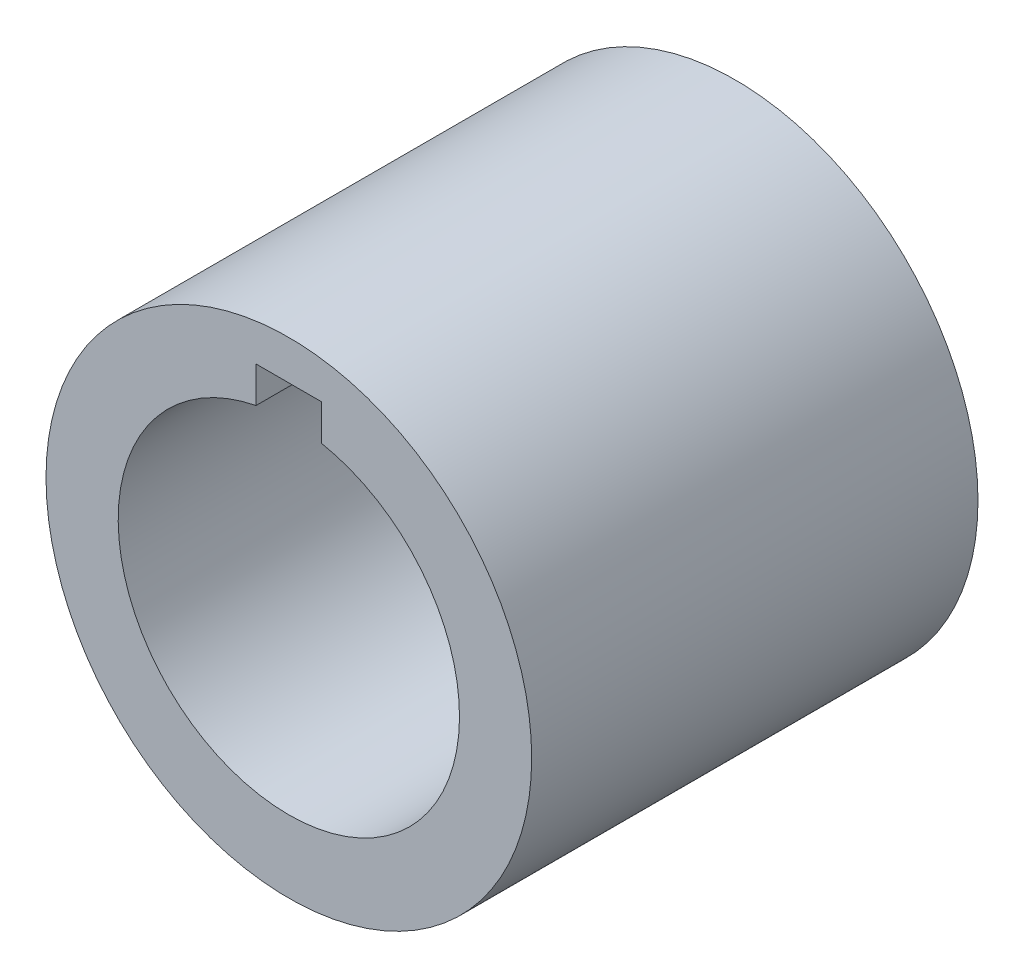
SolidWorks part; units mm, degrees
ref_plane "Front Plane" through (0, 0, 0) normal (0, 0, 1) x (1, 0, 0)
ref_plane "Top Plane" through (0, 0, 0) normal (0, 1, 0) x (1, 0, 0)
ref_plane "Right Plane" through (0, 0, 0) normal (1, 0, 0) x (0, 0, -1)
sketch "Sketch1" plane through (0, 0, 0) normal (0, 0, 1) x (1, 0, 0)
  circle A0 centre (0, 0) radius 13
  circle A1 centre (0, 0) radius 18.5
  dimension "D1" = 26
  dimension "D2" = 37
extrude "Boss-Extrude1" add sketch "Sketch1" along normal blind 34
sketch "Sketch2" plane through (0, 0, 34) normal (0, 0, 1) x (1, 0, 0)
  line L1 (2.5, 15.5) -> (-2.5, 15.5)
  line L2 (2.5, 15.5) -> (2.5, 10.5)
  line L3 (2.5, 10.5) -> (-2.5, 10.5)
  line L4 (-2.5, 15.5) -> (-2.5, 10.5)
  line L5 (2.5, 15.5) -> (-2.5, 10.5) construction
  line L6 (2.5, 10.5) -> (-2.5, 15.5) construction
  circle A0 centre (0, 0) radius 13 construction
  point P0 (0, 13)
  dimension "D1" = 5
  dimension "D2" = 5
extrude "Cut-Extrude1" cut sketch "Sketch2" against normal blind 25.5
fillet "Fillet2" radius 2.5 1 edges at (2.5, 14.1287, 8.5)
fillet "Fillet3" radius 2.5 1 edges at (-2.5, 14.1287, 8.5)
